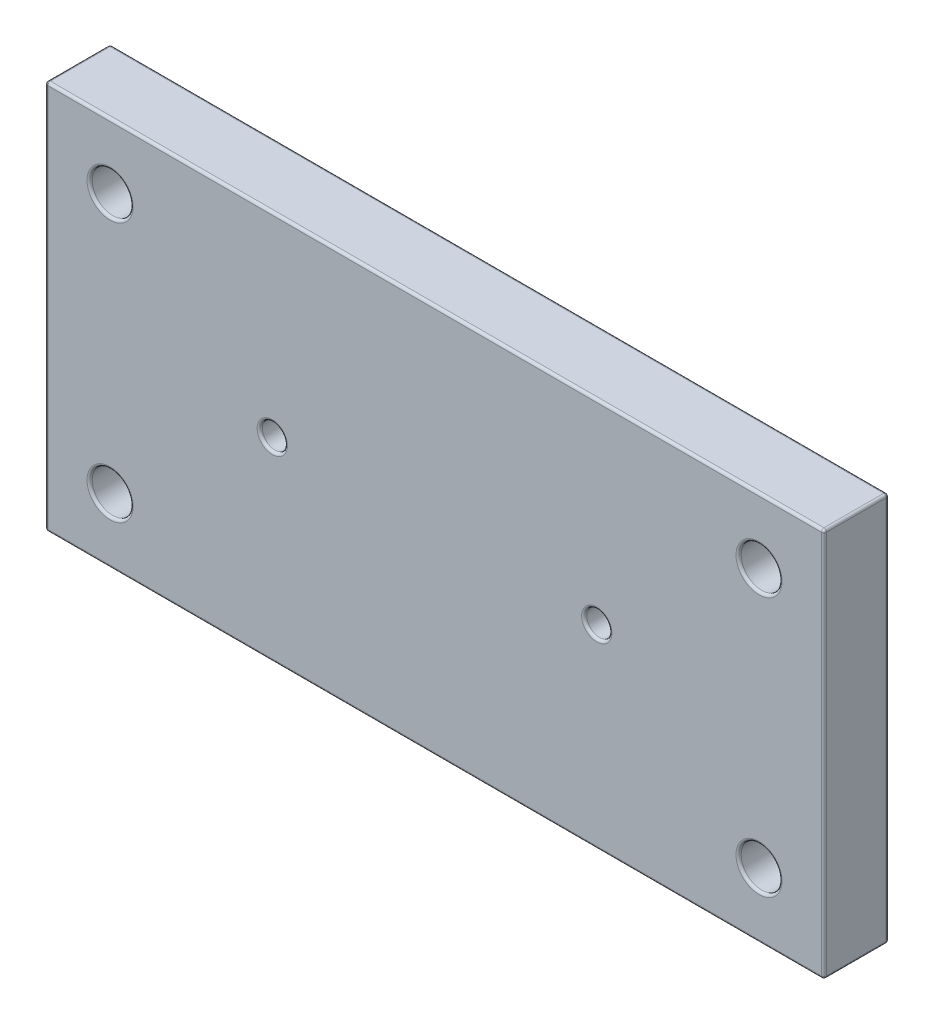
SolidWorks part; units mm, degrees
ref_plane "Front Plane" through (0, 0, 0) normal (0, 0, 1) x (1, 0, 0)
ref_plane "Top Plane" through (0, 0, 0) normal (0, 1, 0) x (1, 0, 0)
ref_plane "Right Plane" through (0, 0, 0) normal (1, 0, 0) x (0, 0, -1)
sketch "Sketch1" plane through (0, 0, 0) normal (0, 0, 1) x (1, 0, 0)
  line L1 (0, 0) -> (152.4, 0)
  line L2 (0, 0) -> (0, 76.2)
  line L3 (0, 76.2) -> (152.4, 76.2)
  line L4 (152.4, 0) -> (152.4, 76.2)
  dimension "D1" = 152.4
  dimension "D2" = 76.2
extrude "Extrude1" add sketch "Sketch1" along normal blind 12.7
hole_wizard "Ø8.0 (8) Diameter Hole1" positions "3DSketch1" profile "Sketch2" hole size "Ø8.0" standard "Ansi Metric" end condition up to next
sketch3d "3DSketch1"
  line L0 (152.4, 76.2, 12.7) -> (0, 76.2, 12.7) construction
  line L1 (0, 76.2, 12.7) -> (0, 0, 12.7) construction
  line L2 (152.4, 0, 12.7) -> (152.4, 76.2, 12.7) construction
  line L3 (0, 0, 12.7) -> (152.4, 0, 12.7) construction
  point P0 (139.7, 63.5, 12.7)
  point P2 (139.7, 12.7, 12.7)
  point P4 (12.7, 12.7, 12.7)
  point P6 (12.7, 63.5, 12.7)
  dimension "D1" = 12.7
  dimension "D2" = 12.7
  dimension "D3" = 12.7
  dimension "D4" = 12.7
  dimension "D5" = 12.7
  dimension "D6" = 12.7
  dimension "D7" = 12.7
  dimension "D8" = 12.7
sketch "Sketch2" plane through (139.7, 63.5, 12.7) normal (1, 0, 0) x (0, -1, 0)
  line L0 (0, 0) -> (0, 12.7)
  line L1 (0, 12.7) -> (4, 12.7)
  line L2 (4, 12.7) -> (4, 0)
  line L5 (4, 0) -> (0, 0)
  line L11 (0, -6.35) -> (0, 107.95) construction
  dimension "Thru Hole Dia." = 8
  dimension "Thru Hole Depth" = 12.7
hole_wizard "#10 (0.1935) Diameter Hole1" positions "3DSketch2" profile "Sketch3" hole size "#10" standard "Ansi Inch" end condition up to next
sketch3d "3DSketch2"
  line L0 (0, 0, 12.7) -> (152.4, 0, 12.7) construction
  line L1 (0, 76.2, 12.7) -> (0, 0, 12.7) construction
  point P0 (44.45, 38.1, 12.7)
  point P2 (107.95, 38.1, 12.7)
  dimension "D1" = 63.5
  dimension "D2" = 38.1
  dimension "D3" = 38.1
  dimension "D4" = 44.45
sketch "Sketch3" plane through (44.45, 38.1, 12.7) normal (1, 0, 0) x (0, -1, 0)
  line L0 (0, 0) -> (0, 12.7)
  line L1 (0, 12.7) -> (2.4574, 12.7)
  line L2 (2.4574, 12.7) -> (2.4574, 0)
  line L5 (2.4574, 0) -> (0, 0)
  line L11 (0, -6.35) -> (0, 107.95) construction
  dimension "Thru Hole Dia." = 4.9149
  dimension "Thru Hole Depth" = 12.7
fillet "Fillet1" radius 0.508 24 edges at (152.4, 0, 6.35) (152.4, 76.2, 6.35) (0, 76.2, 6.35) (0, 0, 6.35) (76.2, 0, 0) (152.4, 38.1, 0) (76.2, 76.2, 0) (0, 38.1, 0) (8.7, 63.5, 0) (8.7, 12.7, 0) (135.7, 12.7, 0) (135.7, 63.5, 0) (143.7, 63.5, 12.7) (143.7, 12.7, 12.7) (76.2, 76.2, 12.7) (152.4, 38.1, 12.7) (76.2, 0, 12.7) (0, 38.1, 12.7) (16.7, 63.5, 12.7) (16.7, 12.7, 12.7) (105.4925, 38.1, 0) (41.9926, 38.1, 0) (46.9074, 38.1, 12.7) (110.4074, 38.1, 12.7)
